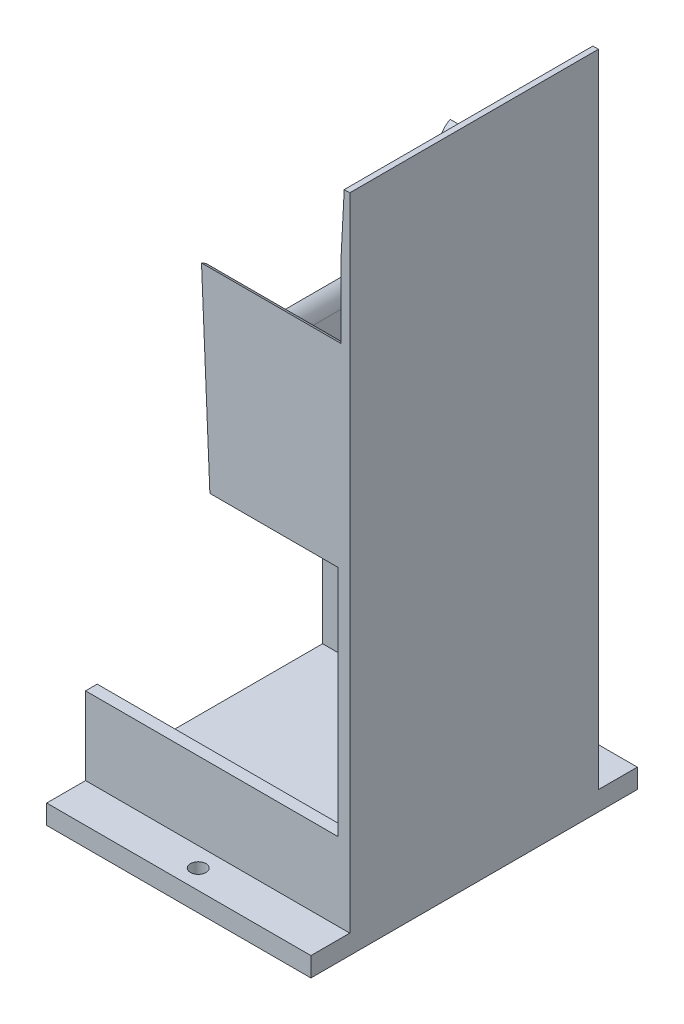
SolidWorks part; units mm, degrees
ref_plane "Front Plane" through (0, 0, 0) normal (0, 0, 1) x (1, 0, 0)
ref_plane "Top Plane" through (0, 0, 0) normal (0, 1, 0) x (1, 0, 0)
ref_plane "Right Plane" through (0, 0, 0) normal (1, 0, 0) x (0, 0, -1)
sketch "Croquis1" plane through (0, 0, 0) normal (0, 1, 0) x (1, 0, 0)
  line L0 (34, 32) -> (34, 42)
  line L1 (-34, -32) -> (34, -32)
  line L2 (-34, -32) -> (-34, 32)
  line L3 (-34, 32) -> (34, 32)
  line L4 (34, -32) -> (34, 32)
  line L5 (-34, -32) -> (34, 32) construction
  line L6 (-34, 32) -> (34, -32) construction
  line L7 (-30.8125, -29) -> (30.8125, -29)
  line L8 (-30.8125, -29) -> (-30.8125, 29)
  line L9 (-30.8125, 29) -> (30.8125, 29)
  line L10 (30.8125, -29) -> (30.8125, 29)
  line L11 (-30.8125, -29) -> (30.8125, 29) construction
  line L12 (-30.8125, 29) -> (30.8125, -29) construction
  line L13 (34, 42) -> (-34, 42)
  line L14 (-34, 42) -> (-34, 32)
  line L15 (0, 0) -> (-15.1383, 0) construction
  line L16 (-34, -42) -> (-34, -32)
  line L17 (34, -42) -> (-34, -42)
  line L18 (34, -32) -> (34, -42)
  circle A0 centre (0, 37) radius 2
  circle A1 centre (0, -37) radius 2
  point P0 (0, 0)
  point P6 (0, 0)
  point P18 (-34, 37)
  point P20 (0, 32)
  dimension "D4" = 4
  dimension "D1" = 68
  dimension "D2" = 64
  dimension "D3" = 3
  dimension "D5" = 10
extrude "Saliente-Extruir1" add sketch "Croquis1" along normal blind 25 contours L1 L4 L3 L2 L10 L7 L8 L9 region at (33.0662, 0, 0)
sketch "Croquis2" plane through (0, 25, 0) normal (0, 1, 0) x (1, 0, 0)
  line L1 (0, 29) -> (0, 32)
  line L4 (-34, -32) -> (34, -32) construction
  line L6 (0, -32) -> (0, -29)
  line L12 (0, 32) -> (34, 32)
  line L14 (34, 32) -> (34, -32)
  line L15 (34, -32) -> (0, -32)
  line L19 (0, -29) -> (30.8125, -29)
  line L20 (30.8125, -29) -> (30.8125, 29)
  line L21 (30.8125, 29) -> (0, 29)
  line L30 (-30.8125, 29) -> (30.8125, 29) construction
  line L31 (-34, 32) -> (34, 32) construction
  dimension "D1" = 0
  dimension "D2" = 0
  dimension "D3" = 0
extrude "Saliente-Extruir2" add sketch "Croquis2" along normal blind 160
sketch "Croquis3" plane through (0, 0, 29) normal (0, 0, -1) x (-1, 0, 0)
  line L5 (0, 155) -> (5, 155)
  line L7 (5, 155) -> (2, 85)
  line L8 (2, 85) -> (0, 85)
  line L12 (0, 185) -> (0, 25) construction
  line L13 (0, 155) -> (0, 85)
  dimension "D1" = 30
  dimension "D2" = 70
  dimension "D3" = 5
  dimension "D4" = 2
extrude "Saliente-Extruir3" add sketch "Croquis3" along normal blind 61 separate body contours L8 L7 L5 region at (-1.8571, 125, 29)
extrude "Saliente-Extruir5" add sketch "Croquis3<4>" against normal blind 3
sketch "Croquis3<4>" plane through (0, 0, 29) normal (0, 0, -1) x (-1, 0, 0) same geometry as "Croquis3"
sketch "Croquis4" plane through (0, 0, -32) normal (0, 0, -1) x (-1, 0, 0)
  line L0 (-31, 185) -> (-31, 155)
  line L2 (-31, 155) -> (69, 155)
  line L3 (69, 155) -> (69, 185)
  line L4 (69, 185) -> (-31, 185)
  line L5 (-34, 185) -> (-34, 0) construction
  line L7 (-34, 185) -> (0, 185) construction
  dimension "D1" = 3
  dimension "D2" = 100
  dimension "D3" = 30
  dimension "D4" = 30
extrude "Cortar-Extruir1" cut sketch "Croquis4" against normal blind 83
chamfer "Chaflán1" distance 2 angle 88 1 edges at (0, 155, 0) first distance on face at (15.4063, 155, 0)
extrude "Saliente-Extruir6" add sketch "Croquis1<2>" along normal blind 5 contours L1 L4 L3 L2 L10 L7 L8 L9 | L7 L10 L9 L8 region at (33.0662, 0, 0) region at (0, 0, 0)
sketch "Croquis1<2>" plane through (0, 0, 0) normal (0, 1, 0) x (1, 0, 0) same geometry as "Croquis1"
sketch "Croquis5" plane through (0, 0, -32) normal (0, 0, -1) x (-1, 0, 0)
  line L0 (9, 25) -> (-31, 25)
  line L1 (-31, 25) -> (-31, 85)
  line L2 (-31, 85) -> (9, 85)
  line L3 (9, 85) -> (9, 25)
  line L4 (-34, 185) -> (-34, 0) construction
  line L5 (34, 0) -> (-34, 0) construction
  dimension "D1" = 3
  dimension "D2" = 60
  dimension "D3" = 40
  dimension "D4" = 25
extrude "Cortar-Extruir2" cut sketch "Croquis5" against normal blind 90
extrude "Saliente-Extruir7" add sketch "Croquis1<4>" along normal blind 5 contours L13 L14 L3 L0 A0 | L18 L1 L16 L17 A1 region at (0, 0, -32.6873) region at (33.3127, 0, 37)
sketch "Croquis1<4>" plane through (0, 0, 0) normal (0, 1, 0) x (1, 0, 0) same geometry as "Croquis1"
sketch "Croquis6" plane through (31, 0, 0) normal (-1, 0, 0) x (0, 0, 1)
  line L6 (-32, 185) -> (-32, 170)
  line L7 (-32, 185) -> (-32, 155) construction
  line L8 (-32, 170) -> (43.448, 170)
  line L9 (43.448, 170) -> (43.448, 185)
  line L10 (43.448, 185) -> (-32, 185)
  dimension "D1" = 15
  dimension "D2" = 75.448
extrude "Cortar-Extruir3" cut sketch "Croquis6" against normal blind 5
chamfer "Chaflán2" distance 30 angle 3 1 edges at (31, 170, 0) first distance on face at (31, 162.5, 0)
chamfer "Chaflán3" distance 5 angle 10 1 edges at (30.8125, 155, 0) first distance on face at (30.8125, 120, 0)
sketch "Croquis7" plane through (-34, 0, 0) normal (-1, 0, 0) x (0, 0, 1)
  line L0 (-29, 25) -> (29, 25)
  line L1 (32, 25) -> (-32, 25) construction
  line L2 (29, 25) -> (29, 5)
  line L3 (29, 5) -> (-29, 5)
  line L4 (-29, 5) -> (-29, 25)
  line L5 (-32, 25) -> (-32, 5) construction
  line L6 (32, 25) -> (32, 5) construction
  line L7 (42, 0) -> (-42, 0) construction
  dimension "D1" = 3
  dimension "D2" = 3
  dimension "D3" = 5
extrude "Cortar-Extruir4" cut sketch "Croquis7" against normal blind 40
sketch "Croquis8" plane through (1.6398, 0.0703, 0) normal (-0.9991, -0.0428, 0) x (0, 0, 1)
  line L0 (-29, 155.0719) -> (29, 155.0719)
  line L2 (29, 155.0719) -> (29, 115.0719)
  line L3 (29, 115.0719) -> (-29, 115.0719)
  line L4 (-29, 115.0719) -> (-29, 155.0719)
  line L6 (-32, 155.0719) -> (-32, 85.0077) construction
  line L7 (32, 85.0077) -> (32, 155.0719) construction
  line L8 (32, 155.0719) -> (-32, 155.0719) construction
  dimension "D1" = 3
  dimension "D2" = 3
  dimension "D3" = 40
extrude "Cortar-Extruir5" cut sketch "Croquis8" against normal blind 10
fillet "Redondeo2" radius 5 1 edges at (-0.6085, 115.1515, 0)
sketch "Croquis9" plane through (0, 0, 32) normal (0, 0, 1) x (1, 0, 0)
  line L0 (-4.1548, 135.279) -> (-3.7153, 125.0234)
  line L3 (-4.263, 155) -> (31.7861, 155)
  line L4 (31.7861, 137.8034) -> (31.7861, 155)
  line L5 (-5, 155) -> (-4.1548, 135.279)
  line L6 (-2, 85) -> (-5, 155) construction
  line L7 (-4.1548, 135.279) -> (31.7861, 135.279)
  line L8 (31.7861, 135.279) -> (31.7861, 137.8034)
  line L9 (-3.7153, 125.0234) -> (31.7861, 125.0234)
  line L10 (31.7861, 125.0234) -> (31.7861, 135.279)
  line M7 (31.7861, 155) -> (-5, 155)
  line M8 (-5, 155) -> (-2, 85)
  dimension "D1" = 35.9409
extrude "Cortar-Extruir6" cut sketch "Croquis9" against normal blind 70 contours L7 L8 L4 M7 M8 region at (13.6035, 145.1777, 32)
fillet "Redondeo5" radius 5 3 edges at (13.3288, 135.279, 29) (13.3288, 135.279, -29) (30.8125, 135.279, 0)
